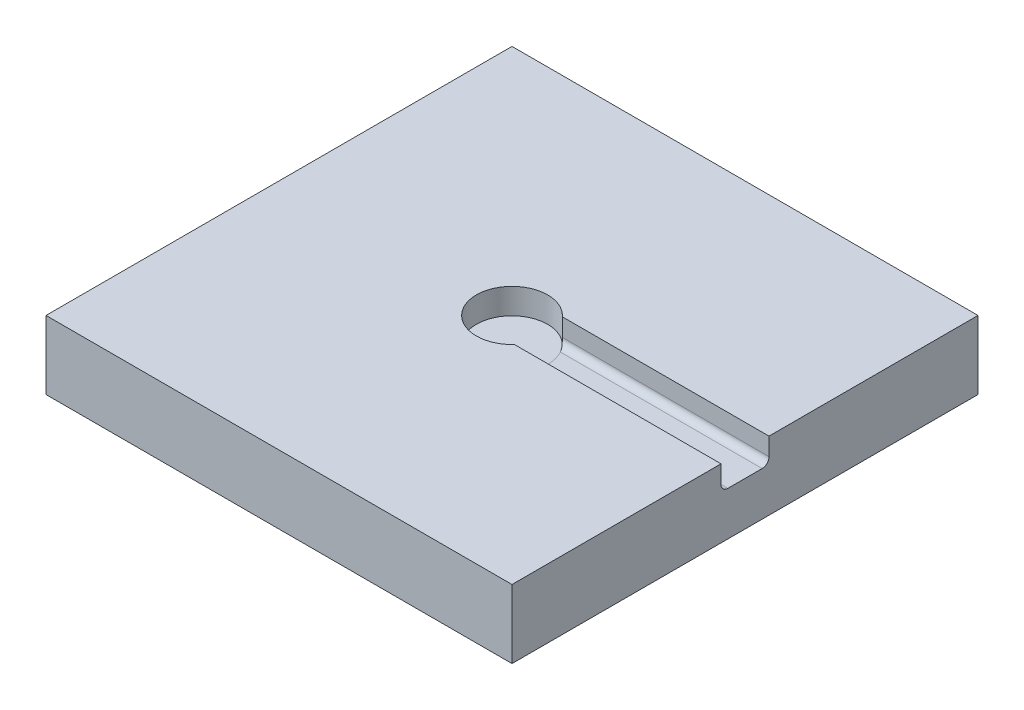
SolidWorks part; units mm, degrees
ref_plane "Front Plane" through (0, 0, 0) normal (0, 0, 1) x (1, 0, 0)
ref_plane "Top Plane" through (0, 0, 0) normal (0, 1, 0) x (1, 0, 0)
ref_plane "Right Plane" through (0, 0, 0) normal (1, 0, 0) x (0, 0, -1)
sketch "Sketch1" plane through (0, 0, 0) normal (0, 1, 0) x (1, 0, 0)
  line L1 (170, 170) -> (-170, 170)
  line L2 (170, 170) -> (170, -170)
  line L3 (170, -170) -> (-170, -170)
  line L4 (-170, 170) -> (-170, -170)
  line L5 (170, 170) -> (-170, -170) construction
  line L6 (170, -170) -> (-170, 170) construction
  point P0 (0, 0)
  dimension "D1" = 340
  dimension "D2" = 340
extrude "Boss-Extrude1" add sketch "Sketch1" along normal blind 50
sketch "Sketch2" plane through (0, 50, 0) normal (0, 1, 0) x (1, 0, 0)
  circle A0 centre (0, 0) radius 26
  dimension "D1" = 52
extrude "Cut-Extrude1" cut sketch "Sketch2" against normal blind 18.6 contours A0
sketch "Sketch3" plane through (170, 0, 0) normal (1, 0, 0) x (0, 0, -1)
  line L1 (-17.5, 32) -> (17.5, 32)
  line L2 (-17.5, 32) -> (-17.5, 50)
  line L3 (-17.5, 50) -> (17.5, 50)
  line L4 (17.5, 32) -> (17.5, 50)
  line L5 (-170, 50) -> (170, 50) construction
  line L6 (-170, 0) -> (170, 0) construction
  point P6 (0, 32)
  point P10 (0, 0)
  dimension "D1" = 18
  dimension "D2" = 35
extrude "Cut-Extrude2" cut sketch "Sketch3" against normal blind 170
fillet "Fillet1" radius 5 2 edges at (94.6144, 32, 17.5) (94.6144, 32, -17.5)
